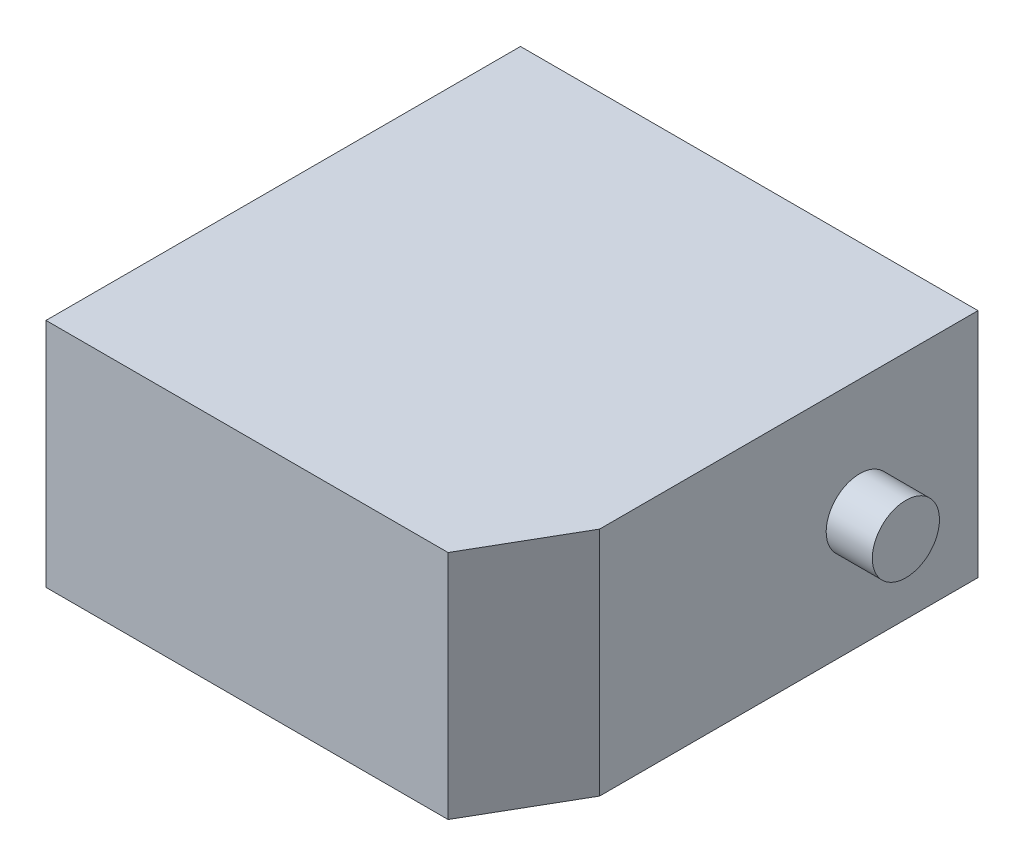
SolidWorks part; units mm, degrees
ref_plane "Front Plane" through (0, 0, 0) normal (0, 0, 1) x (1, 0, 0)
ref_plane "Top Plane" through (0, 0, 0) normal (0, 1, 0) x (1, 0, 0)
ref_plane "Right Plane" through (0, 0, 0) normal (1, 0, 0) x (0, 0, -1)
sketch "Sketch1" plane through (0, 0, 0) normal (0, 1, 0) x (1, 0, 0)
  line L0 (19.9009, -12.2786) -> (15.0749, -20.6375)
  line L1 (-19.9009, -20.6375) -> (15.0749, -20.6375)
  line L2 (-19.9009, -20.6375) -> (-19.9009, 20.6375)
  line L3 (-19.9009, 20.6375) -> (19.9009, 20.6375)
  line L4 (19.9009, -12.2786) -> (19.9009, 20.6375)
  line L5 (-19.9009, -20.6375) -> (19.9009, 20.6375) construction
  line L6 (-19.9009, 20.6375) -> (19.9009, -20.6375) construction
  line L7 (15.0749, -20.6375) -> (19.9009, -20.6375) construction
  line L8 (19.9009, -20.6375) -> (19.9009, -12.2786) construction
  point P0 (0, 0)
  dimension "D1" = 41.275
  dimension "D2" = 39.8018
  dimension "D3" = 60
  dimension "D4" = 4.826
extrude "Boss-Extrude1" add sketch "Sketch1" along normal blind 20.1168
sketch "Sketch2" plane through (19.9009, 0, 0) normal (1, 0, 0) x (0, 0, -1)
  line L0 (20.6375, 10.0584) -> (-12.2786, 10.0584) construction
  line L1 (20.6375, 20.1168) -> (20.6375, 0) construction
  line L2 (-12.2786, 20.1168) -> (-12.2786, 0) construction
  circle A0 centre (10.3505, 10.0584) radius 2.921
  dimension "D1" = 5.842
  dimension "D2" = 7.366
extrude "Boss-Extrude2" add sketch "Sketch2" along normal blind 4.0132
